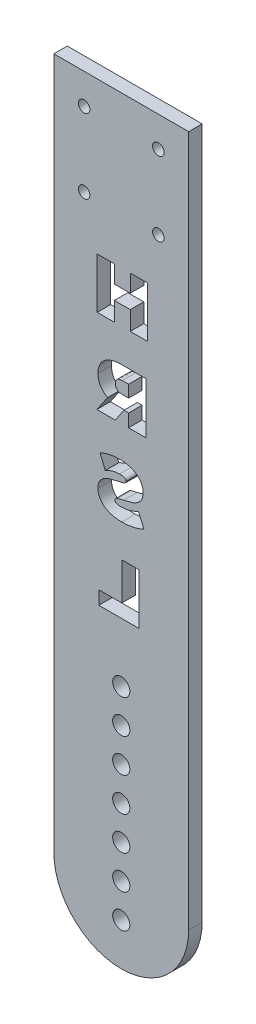
SolidWorks part; units mm, degrees
other "Markup1"
sketch "Sketch7" plane through (-20, 225, -2) normal (-0.1146, 0.1086, -0.9875) x (-0.991, 0.0573, 0.1213)
ref_plane "Front Plane" through (0, 0, 0) normal (0, 0, 1) x (1, 0, 0)
ref_plane "Top Plane" through (0, 0, 0) normal (0, 1, 0) x (1, 0, 0)
ref_plane "Right Plane" through (0, 0, 0) normal (1, 0, 0) x (0, 0, -1)
sketch "Sketch1" plane through (0, 0, 0) normal (0, 1, 0) x (1, 0, 0)
  line L1 (-20, 2) -> (20, 2)
  line L2 (-20, 2) -> (-20, -2)
  line L3 (-20, -2) -> (20, -2)
  line L4 (20, 2) -> (20, -2)
  line L5 (-20, 2) -> (20, -2) construction
  line L6 (-20, -2) -> (20, 2) construction
  point P0 (0, 0)
extrude "Boss-Extrude1" add sketch "Sketch1" along normal blind 225
fillet "Fillet1" radius 20 2 edges at (-20, 0, 0) (20, 0, 0)
sketch "Sketch2" plane through (0, 0, 2) normal (0, 0, 1) x (1, 0, 0)
  circle A0 centre (0, 12.5) radius 2.55
  dimension "D1" = 12.5
extrude "Cut-Extrude1" cut sketch "Sketch2" against normal through all
pattern_linear "LPattern1" count 7 spacing 10 along (0, 1, 0) of "Cut-Extrude1"
sketch "Sketch8" plane through (0, 0, -2) normal (0, 0, -1) x (-1, 0, 0)
  line L0 (-20, 225) -> (20, 225) construction
  line L1 (-20, 225) -> (-20, 20) construction
  line L2 (20, 225) -> (20, 20) construction
  line L3 (-20, 185) -> (20, 185) construction
  circle A0 centre (-11, 216) radius 1.7
  circle A1 centre (11, 216) radius 1.7
  circle A2 centre (-11, 194) radius 1.7
  circle A3 centre (11, 194) radius 1.7
  dimension "D1" = 9
  dimension "D3" = 9
  dimension "D5" = 3.4
  dimension "D2" = 9
  dimension "D4" = 9
  dimension "D6" = 40
  dimension "D7" = 9
extrude "Cut-Extrude4" cut sketch "Sketch8" against normal through all
sketch "Sketch9" plane through (0, 0, -2) normal (0, 0, -1) x (-1, 0, 0)
  line L0 (0, 182.004) -> (0, 90.0353) construction
  text T0 "<b><r0>H</r></b>" font "Montserrat Black" height 15
  text T1 "<b>R</b>" font "Montserrat Black" height 15
  text T2 "<b>S</b>" font "Montserrat Black" height 15
  text T3 "<b>L</b>" font "Montserrat Black" height 15
  point P7 (0, 140.0353)
  point P8 (0, 165.0353)
  point P9 (0, 115.0353)
  point P10 (0, 0)
  point P11 (0, 0)
  point P12 (0, 0)
  point P13 (0, 0)
  point P14 (0, 0)
  dimension "D1" = 25
  dimension "D2" = 25
  dimension "D3" = 25
  dimension "D4" = 9
  dimension "D5" = 8.5
  dimension "D6" = 7
  dimension "D7" = 6.5
extrude "Cut-Extrude5" cut sketch "Sketch9" against normal through all
